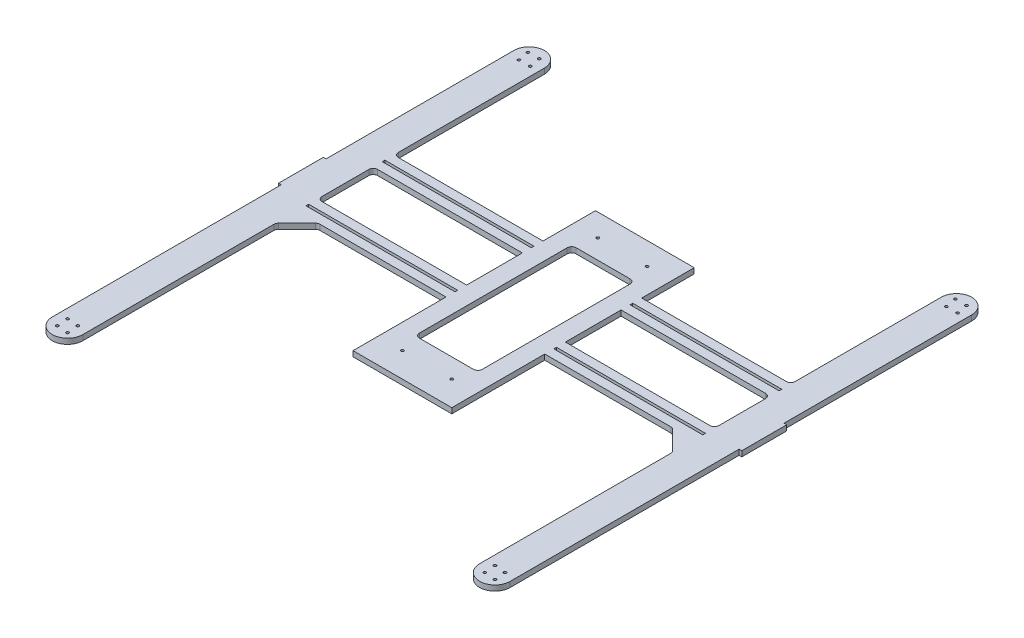
SolidWorks part; units mm, degrees
ref_plane "Front Plane" through (0, 0, 0) normal (0, 0, 1) x (1, 0, 0)
ref_plane "Top Plane" through (0, 0, 0) normal (0, 1, 0) x (1, 0, 0)
ref_plane "Right Plane" through (0, 0, 0) normal (1, 0, 0) x (0, 0, -1)
sketch "Sketch1" plane through (0, 0, 0) normal (0, 1, 0) x (1, 0, 0)
  line L1 (216, -40) -> (216, -255)
  line L4 (216, 78.5) -> (216, 81.5)
  line L5 (250, -255) -> (250, 0)
  line L6 (50, -120) -> (250, -120) construction
  line L7 (50, 150) -> (50, 91.5) construction
  line L8 (50, 150) -> (250, 120) construction
  line L10 (227.9078, 252.8902) -> (238.0922, 265.2304) construction
  line L11 (240.327, 253.0134) -> (225.673, 265.1073) construction
  line L12 (227.3431, -260.6569) -> (238.6569, -249.3431) construction
  line L13 (0, 25) -> (250, 25) construction
  line L14 (226.2825, -248.2825) -> (239.7175, -261.7175) construction
  line L18 (250, 0) -> (253, 0)
  line L19 (253, 0) -> (253, 50)
  line L20 (253, 50) -> (250, 50)
  line L21 (250, 50) -> (250, 259.0603)
  line L22 (50, 81.5) -> (50, 78.5) construction
  line L23 (50, 81.5) -> (50, 78.5)
  line L24 (50, -3.5) -> (50, -6.5) construction
  line L25 (50, -16.5) -> (50, -120) construction
  line L26 (50, 68.5) -> (50, 6.5)
  line L27 (-60, -5) -> (-226, -5) construction
  line L28 (216, 68.5) -> (216, 6.5)
  line L29 (-226, 68.5) -> (-226, 6.5)
  line L47 (-5, 150) -> (-5, -120) construction
  line L48 (-60, -120) -> (50, -120)
  line L53 (-60, 150) -> (50, 150)
  line L54 (50, 150) -> (50, 91.5)
  line L57 (250, -120) -> (250, -5) construction
  line L58 (50, -3.5) -> (50, -6.5)
  line L59 (216, -6.5) -> (50, -6.5)
  line L60 (50, 80) -> (216, 80) construction
  line L61 (250, 80) -> (250, 81.5) construction
  line L62 (216, 81.5) -> (50, 81.5)
  line L63 (216, -3.5) -> (50, -3.5)
  line L64 (250, 80) -> (250, 78.5) construction
  line L65 (216, 78.5) -> (50, 78.5)
  line L66 (-60, 80) -> (-226, 80) construction
  line L67 (50, 91.5) -> (216, 91.5)
  line L68 (-260, -120) -> (-260, -5) construction
  line L69 (50, 68.5) -> (216, 68.5)
  line L70 (50, -120) -> (50, -16.5)
  line L71 (-60, -16.5) -> (-60, -120) construction
  line L72 (50, -16.5) -> (192.5, -16.5)
  line L73 (-60, -3.5) -> (-60, -6.5) construction
  line L74 (50, 6.5) -> (216, 6.5)
  line L75 (192.5, -16.5) -> (216, -40)
  line L76 (50, -5) -> (216, -5) construction
  line L79 (216, -6.5) -> (216, -3.5)
  line L80 (216, 91.5) -> (216, 259.0603)
  line L81 (-60, 81.5) -> (-60, 78.5) construction
  line L83 (-10, 25) -> (-260, 25) construction
  line L84 (-237.3431, -260.6569) -> (-248.6569, -249.3431) construction
  line L85 (-248.6569, -260.6569) -> (-237.3431, -249.3431) construction
  line L87 (-60, 150) -> (-260, 120) construction
  line L88 (-60, 150) -> (-60, 91.5) construction
  line L89 (-60, -120) -> (-260, -120) construction
  line L90 (-226, 91.5) -> (-226, 259.0603)
  line L91 (-226, -6.5) -> (-226, -3.5)
  line L93 (-202.5, -16.5) -> (-226, -40)
  line L94 (-60, 6.5) -> (-226, 6.5)
  line L95 (-60, -16.5) -> (-202.5, -16.5)
  line L96 (-60, -120) -> (-60, -16.5)
  line L97 (-60, 68.5) -> (-226, 68.5)
  line L98 (-60, 91.5) -> (-226, 91.5)
  line L99 (-226, 78.5) -> (-60, 78.5)
  line L100 (-226, -3.5) -> (-60, -3.5)
  line L101 (-226, 81.5) -> (-60, 81.5)
  line L102 (-226, -6.5) -> (-60, -6.5)
  line L103 (-60, -3.5) -> (-60, -6.5)
  line L104 (-60, 150) -> (-60, 91.5)
  line L105 (-60, 68.5) -> (-60, 6.5)
  line L106 (-60, 81.5) -> (-60, 78.5)
  line L107 (-260, 50) -> (-260, 259.0603)
  line L108 (-263, 50) -> (-260, 50)
  line L109 (-263, 0) -> (-263, 50)
  line L110 (-260, 0) -> (-263, 0)
  line L111 (-260, -255) -> (-260, 0)
  line L112 (-226, 78.5) -> (-226, 81.5)
  line L113 (-226, -40) -> (-226, -255)
  line L116 (-235.673, 253.0134) -> (-250.327, 265.1073) construction
  line L119 (-248.0922, 252.8902) -> (-237.9078, 265.2304) construction
  line L121 (30, 103.5) -> (30, -71)
  line L122 (30, 103.5) -> (-40, 103.5)
  line L123 (-40, 103.5) -> (-40, -71)
  line L124 (-40, -71) -> (30, -71)
  arc A0 (216, -255) -> (250, -255) centre (233, -255) ccw
  arc A1 (216, 259.0603) -> (250, 259.0603) centre (233, 259.0603) cw
  circle A2 centre (233, -255) radius 135 construction
  circle A3 centre (233, 259.0603) radius 135 construction
  circle A4 centre (238.0922, 265.2304) radius 1.5
  circle A5 centre (225.673, 265.1073) radius 1.5
  circle A6 centre (227.9078, 252.8902) radius 1.5
  circle A7 centre (240.327, 253.0134) radius 1.5
  circle A8 centre (226.2825, -248.2825) radius 1.5
  circle A9 centre (238.6569, -249.3431) radius 1.5
  circle A10 centre (239.7175, -261.7175) radius 1.5
  circle A11 centre (227.3431, -260.6569) radius 1.5
  circle A33 centre (22.5, 125) radius 1.5
  circle A36 centre (-243, 259.0603) radius 135 construction
  circle A37 centre (-243, -255) radius 135 construction
  circle A39 centre (-32.5, 125) radius 1.5
  arc A48 (-226, 259.0603) -> (-260, 259.0603) centre (-243, 259.0603) ccw
  arc A49 (-226, -255) -> (-260, -255) centre (-243, -255) cw
  circle A50 centre (22.5, -92.5) radius 1.5
  circle A51 centre (-32.5, -92.5) radius 1.5
  circle A52 centre (-235.673, 253.0134) radius 1.5
  circle A53 centre (-237.9078, 265.2304) radius 1.5
  circle A54 centre (-248.0922, 252.8902) radius 1.5
  circle A55 centre (-250.327, 265.1073) radius 1.5
  circle A56 centre (-249.7175, -248.2825) radius 1.5
  circle A57 centre (-236.2825, -261.7175) radius 1.5
  circle A58 centre (-248.6569, -260.6569) radius 1.5
  circle A59 centre (-237.3431, -249.3431) radius 1.5
  point P12 (250, 120)
  point P13 (250, -120)
  point P15 (50, -120)
  point P134 (-60, -120)
  point P135 (-260, -120)
  point P136 (-260, 120)
  dimension "D1" = 17
  dimension "D3" = 270
  dimension "D4" = 270
  dimension "D12" = 3
  dimension "D13" = 3
  dimension "D14" = 3
  dimension "D15" = 3
  dimension "D20" = 3
  dimension "D21" = 3
  dimension "D22" = 3
  dimension "D23" = 3
  dimension "D7" = 16
  dimension "D11" = 3
  dimension "D5" = 240
  dimension "D6" = 200
  dimension "D8" = 19
  dimension "D9" = 16
  dimension "D10" = 19
  dimension "D16" = 270
  dimension "D17" = 45
  dimension "D18" = 16
  dimension "D19" = 19
extrude "Boss-Extrude1" add sketch "Sketch1" along normal blind 6 contours L1 A0 L5 L8 L4 L7 A11 A10 A9 A8 | L7 | A1 L4 L8 L5 A7 A6 A5 A4 region at (209.5727, 0, 22.9273)
fillet "Скругление1" radius 5 14 edges at (216, 3, -6.5) (216, 3, -68.5) (216, 3, -91.5) (-226, 3, -6.5) (-226, 3, -68.5) (-226, 3, -91.5) (-226, 3, 40) (-202.5, 3, 16.5) (216, 3, 40) (192.5, 3, 16.5) (-40, 3, 71) (30, 3, 71) (30, 3, -103.5) (-40, 3, -103.5)
